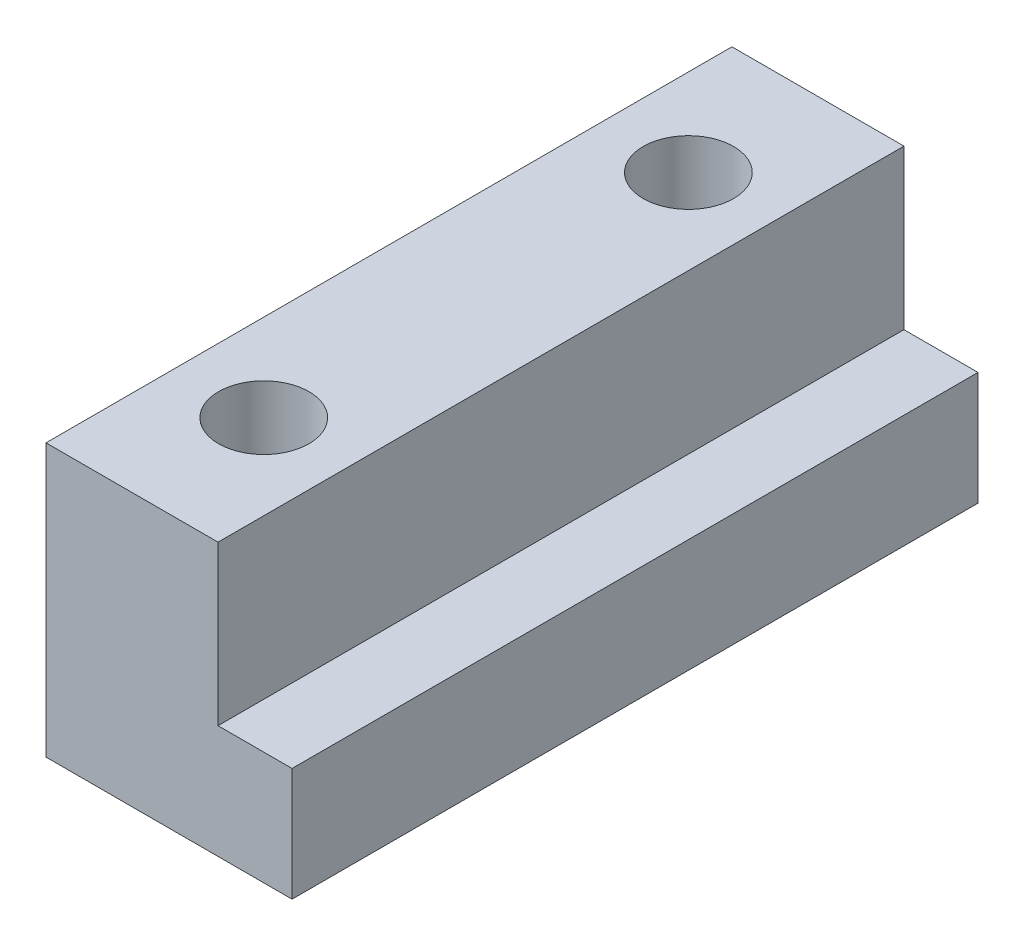
SolidWorks part; units mm, degrees
ref_plane "Front Plane" through (0, 0, 0) normal (0, 0, 1) x (1, 0, 0)
ref_plane "Top Plane" through (0, 0, 0) normal (0, 1, 0) x (1, 0, 0)
ref_plane "Right Plane" through (0, 0, 0) normal (1, 0, 0) x (0, 0, -1)
sketch "Sketch1" plane through (0, 0, 0) normal (0, 0, 1) x (1, 0, 0)
  line L0 (0, 0) -> (0, 12.5)
  line L1 (0, 12.5) -> (7.9, 12.5)
  line L2 (7.9, 12.5) -> (7.9, 5.2)
  line L3 (7.9, 5.2) -> (11.3, 5.2)
  line L4 (11.3, 5.2) -> (11.3, 0)
  line L5 (11.3, 0) -> (0, 0)
  dimension "D1" = 11.3
  dimension "D2" = 12.5
  dimension "D3" = 7.9
  dimension "D4" = 5.2
extrude "Boss-Extrude1" add sketch "Sketch1" against normal blind 31.5
sketch "Sketch2" plane through (0, 12.5, 0) normal (0, 1, 0) x (1, 0, 0)
  line L0 (7.9, 31.5) -> (0, 31.5) construction
  line L1 (0, 31.5) -> (0, 0) construction
  line L2 (7.9, 0) -> (0, 0) construction
  circle A0 centre (4, 6) radius 2.075
  circle A1 centre (4, 25.5) radius 2.075
  point P4 (0, 0)
  dimension "D1" = 4.15
  dimension "D2" = 6
  dimension "D3" = 4
  dimension "D4" = 6
extrude "Cut-Extrude1" cut sketch "Sketch2" against normal blind 7
